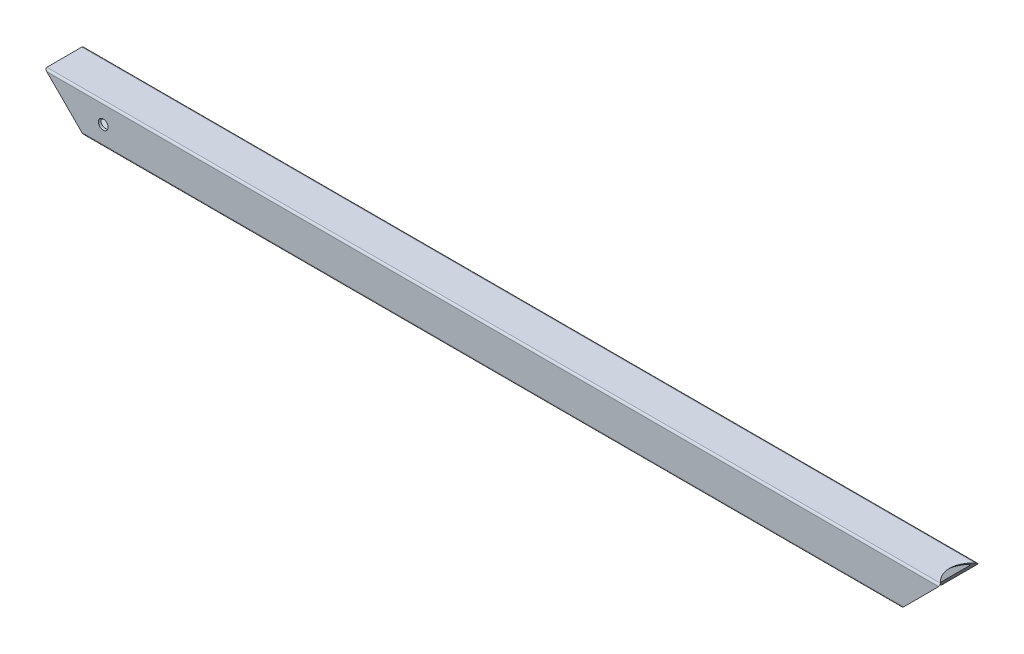
SolidWorks part; units mm, degrees
ref_plane "Front" through (0, 0, 0) normal (0, 0, 1) x (1, 0, 0)
ref_plane "Top" through (0, 0, 0) normal (0, 1, 0) x (1, 0, 0)
ref_plane "Right" through (0, 0, 0) normal (1, 0, 0) x (0, 0, -1)
sketch "Sketch1" plane through (0, 0, 0) normal (1, 0, 0) x (0, 0, -1)
  line L0 (-11.049, 0) -> (-12.7, 0) construction
  line L1 (11.43, -12.7) -> (-11.43, -12.7) construction
  line L2 (12.7, -11.43) -> (12.7, 11.43) construction
  line L3 (11.43, 12.7) -> (-11.43, 12.7) construction
  line L4 (-12.7, -11.43) -> (-12.7, 11.43) construction
  line L5 (12.7, -12.7) -> (-12.7, 12.7) construction
  line L6 (12.7, 12.7) -> (-12.7, -12.7) construction
  line L7 (9.9441, 11.049) -> (-9.9441, 11.049) construction
  line L8 (11.049, 9.9441) -> (11.049, -9.9441) construction
  line L9 (9.9441, -11.049) -> (-9.9441, -11.049) construction
  line L10 (-11.049, 9.9441) -> (-11.049, -9.9441) construction
  line L11 (11.049, 11.049) -> (-11.049, -11.049) construction
  line L12 (11.049, -11.049) -> (-11.049, 11.049) construction
  line L13 (0, -11.049) -> (0, -12.7) construction
  line L14 (11.049, -9.9441) -> (11.049, -12.7) construction
  line L15 (11.049, 0) -> (12.7, 0) construction
  line L16 (11.049, -12.7) -> (12.7, -12.7) construction
  arc A0 (-9.9441, -11.049) -> (-11.049, -9.9441) centre (-9.9441, -9.9441) cw construction
  arc A1 (11.049, -9.9441) -> (9.9441, -11.049) centre (9.9441, -9.9441) cw construction
  arc A2 (9.9441, 11.049) -> (11.049, 9.9441) centre (9.9441, 9.9441) cw construction
  arc A3 (-9.9441, 11.049) -> (-11.049, 9.9441) centre (-9.9441, 9.9441) ccw construction
  arc A4 (11.43, -12.7) -> (12.7, -11.43) centre (11.43, -11.43) ccw construction
  arc A5 (12.7, 11.43) -> (11.43, 12.7) centre (11.43, 11.43) ccw construction
  arc A6 (-11.43, 12.7) -> (-12.7, 11.43) centre (-11.43, 11.43) ccw construction
  arc A7 (-11.43, -12.7) -> (-12.7, -11.43) centre (-11.43, -11.43) cw construction
  point P0 (0, 0)
  point P6 (0, 0)
  dimension "D2" = 1.1049
  dimension "D3" = 1.27
  dimension "Outside Width" = 25.4
  dimension "Ouside Height" = 25.4
  dimension "Inside Height" = 22.098
  dimension "Wall Thickness" = 1.651
sketch "Sketch2" plane through (0, 0, 0) normal (0, 0, 1) x (1, 0, 0)
  line L0 (-292.1, 0) -> (292.1, 0) construction
  point P3 (-268.351, 0)
  point P4 (268.351, 0)
  dimension "Length" = 584.2
  dimension "D1" = 23.749
  dimension "D2" = 23.749
sketch "Sketch4" plane through (0, 0, 0) normal (1, 0, 0) x (0, 0, -1)
  line L8 (12.7, -11.43) -> (12.7, 11.43)
  line L9 (11.43, 12.7) -> (-11.43, 12.7)
  line L10 (-12.7, -11.43) -> (-12.7, 11.43)
  line L11 (11.43, -12.7) -> (-11.43, -12.7)
  line L12 (11.049, 9.9441) -> (11.049, -9.9441)
  line L13 (9.9441, -11.049) -> (-9.9441, -11.049)
  line L14 (-11.049, 9.9441) -> (-11.049, -9.9441)
  line L15 (9.9441, 11.049) -> (-9.9441, 11.049)
  arc A8 (12.7, 11.43) -> (11.43, 12.7) centre (11.43, 11.43) ccw
  arc A9 (-11.43, 12.7) -> (-12.7, 11.43) centre (-11.43, 11.43) ccw
  arc A10 (-12.7, -11.43) -> (-11.43, -12.7) centre (-11.43, -11.43) ccw
  arc A11 (11.43, -12.7) -> (12.7, -11.43) centre (11.43, -11.43) ccw
  arc A12 (9.9441, -11.049) -> (11.049, -9.9441) centre (9.9441, -9.9441) ccw
  arc A13 (-11.049, -9.9441) -> (-9.9441, -11.049) centre (-9.9441, -9.9441) ccw
  arc A14 (-9.9441, 11.049) -> (-11.049, 9.9441) centre (-9.9441, 9.9441) ccw
  arc A15 (11.049, 9.9441) -> (9.9441, 11.049) centre (9.9441, 9.9441) ccw
extrude "Boss-Extrude1" add sketch "Sketch4" along normal up to vertex (-292.1 mm away) and the other way up to vertex (-292.1 mm away) up to point (-292.1, 0, 0) other way up to point (292.1, 0, 0)
sketch "Sketch5" plane through (0, 0, 12.7) normal (0, 0, 1) x (1, 0, 0)
  line L0 (292.1, 12.7) -> (-292.1, 12.7) construction
  line L1 (-292.1, 11.43) -> (-292.1, -11.43) construction
  circle A0 centre (-254, 0) radius 3.175
  dimension "D1" = 12.7
  dimension "D2" = 38.1
  dimension "D3" = 6.35
extrude "Cut-Extrude1" cut sketch "Sketch5" against normal through all
ref_plane "Plane1" through (152.4, 152.4, 0) normal (0.7071, 0.7071, 0) x (0, 0, 1)
sketch "Sketch7" plane through (152.4, 152.4, 0) normal (0.7071, 0.7071, 0) x (0, 0, 1)
  line L0 (11.43, 215.5261) -> (-11.43, 215.5261) construction
  line L1 (-12.7, 214.6281) -> (-12.7, 198.4637) construction
  circle A0 centre (0, 212.2241) radius 19.05
  dimension "D1" = 38.1
  dimension "D2" = 3.302
  dimension "D3" = 12.7
extrude "Cut-Extrude3" cut sketch "Sketch7" against normal through all
sketch "Sketch8" plane through (0, 0, 12.7) normal (0, 0, 1) x (1, 0, 0)
  line L0 (-292.1, 12.7) -> (-266.7, -12.7)
  line L1 (265.8777, -12.7) -> (-292.1, -12.7) construction
  line L2 (-266.7, -12.7) -> (-292.1, -12.7)
  line L3 (-292.1, 12.7) -> (-292.1, -12.7)
  dimension "D1" = 45
extrude "Cut-Extrude4" cut sketch "Sketch8" against normal through all
equation "\"D3@Sketch1\"=\"Outside Width@Sketch1\"*.05"
equation "\"D2@Sketch1\" = \"Inside Height@Sketch1\" * .05"
equation "\"D1@Sketch2\"=\"Outside Width@Sketch1\"-\"Wall Thickness@Sketch1\""
equation "\"D2@Sketch2\"=\"D1@Sketch2\""
